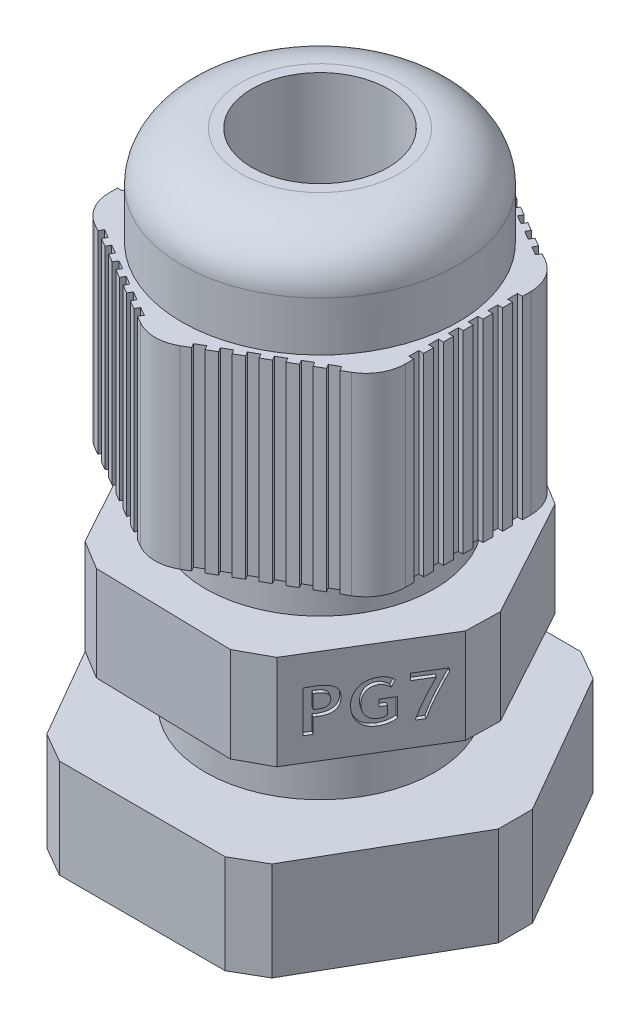
SolidWorks part; units mm, degrees
ref_plane "Front Plane" through (0, 0, 0) normal (0, 0, 1) x (1, 0, 0)
ref_plane "Top Plane" through (0, 0, 0) normal (0, 1, 0) x (1, 0, 0)
ref_plane "Right Plane" through (0, 0, 0) normal (1, 0, 0) x (0, 0, -1)
sketch "Sketch1" plane through (0, 0, 0) normal (0, 1, 0) x (1, 0, 0)
  circle A0 centre (0, 0) radius 5.8
  dimension "D1" = 11.6
extrude "Boss-Extrude1" add sketch "Sketch1" along normal blind 8.25
sketch "Sketch2" plane through (0, 8.25, 0) normal (0, 1, 0) x (1, 0, 0)
  line L1 (8.9465, -0.2087) -> (4.654, 7.6436)
  line L2 (4.654, 7.6436) -> (-4.2925, 7.8522)
  line L3 (-4.2925, 7.8522) -> (-8.9465, 0.2087)
  line L4 (-8.9465, 0.2087) -> (-4.654, -7.6436)
  line L5 (-4.654, -7.6436) -> (4.2925, -7.8522)
  line L6 (4.2925, -7.8522) -> (8.9465, -0.2087)
  circle A0 centre (0, 0) radius 7.75 construction
  dimension "D1" = 15.5
extrude "Boss-Extrude2" add sketch "Sketch2" along normal blind 4.8
sketch "Sketch3" plane through (0, 13.05, 0) normal (0, 1, 0) x (1, 0, 0)
  circle A0 centre (0, 0) radius 5.8
  dimension "D1" = 11.6
extrude "Boss-Extrude3" add sketch "Sketch3" along normal blind 2.5
sketch "Sketch4" plane through (0, 15.55, 0) normal (0, 1, 0) x (1, 0, 0)
  line L1 (7.5, 4.3301) -> (0, 8.6603)
  line L2 (0, 8.6603) -> (-7.5, 4.3301)
  line L3 (-7.5, 4.3301) -> (-7.5, -4.3301)
  line L4 (-7.5, -4.3301) -> (0, -8.6603)
  line L5 (0, -8.6603) -> (7.5, -4.3301)
  line L6 (7.5, -4.3301) -> (7.5, 4.3301)
  circle A0 centre (0, 0) radius 7.5 construction
  dimension "D1" = 15
  dimension "D2" = 0
extrude "Boss-Extrude4" add sketch "Sketch4" along normal blind 9.8
chamfer "Chamfer1" distance 1 distance2 1 6 edges at (-8.9465, 10.65, -0.2087) (-4.654, 10.65, 7.6436) (4.2925, 10.65, 7.8522) (8.9465, 10.65, 0.2087) (4.654, 10.65, -7.6436) (-4.2925, 10.65, -7.8522)
fillet "Fillet1" radius 2 6 edges at (7.5, 20.45, -4.3301) (7.5, 20.45, 4.3301) (0, 20.45, 8.6603) (-7.5, 20.45, 4.3301) (-7.5, 20.45, -4.3301) (0, 20.45, -8.6603)
sketch "Sketch5" plane through (0, 25.35, 0) normal (0, 1, 0) x (1, 0, 0)
  circle A0 centre (0, 0) radius 7
  dimension "D1" = 14
extrude "Boss-Extrude5" add sketch "Sketch5" along normal blind 5
fillet "Fillet2" radius 2.5 1 edges at (0, 30.35, 7) second distance 3 first distance on face at (0, 30.35, 7)
sketch "Sketch6" plane through (0, 30.35, 0) normal (0, 1, 0) x (1, 0, 0)
  circle A0 centre (0, 0) radius 3.45
  dimension "D1" = 6.9
extrude "Cut-Extrude1" cut sketch "Sketch6" against normal up to surface (30.35 mm away) up to face at (0, 0, 5.8)
sketch "Sketch7" plane through (-6.8002, 0, 3.7174) normal (-0.8774, 0, 0.4797) x (0.4797, 0, 0.8774)
  line L0 (-3.4745, 9.45) -> (3.4745, 9.45) construction
  line L1 (-3.4745, 13.05) -> (-3.4745, 8.25) construction
  line L2 (3.4745, 8.25) -> (3.4745, 13.05) construction
  line L3 (-3.4745, 8.25) -> (3.4745, 8.25) construction
  text T0 "<b>PG7</b>" font "Trebuchet MS" height in points 8
  dimension "D1" = 1.2
extrude "Cut-Extrude2" cut sketch "Sketch7" against normal blind 0.2
sketch "Sketch8" plane through (7.5, 0, 0) normal (1, 0, 0) x (0, 0, -1)
  line L0 (0, 25.35) -> (0, 15.55) construction
  line L1 (-3.1754, 25.35) -> (3.1754, 25.35) construction
  line L2 (-5.8, 15.55) -> (5.8, 15.55) construction
  line L3 (0.25, 25.35) -> (0.25, 15.55)
  line L4 (-0.25, 25.35) -> (-0.25, 15.55)
  line L5 (0.25, 25.35) -> (0.75, 25.35)
  line L6 (0.75, 25.35) -> (0.75, 15.55)
  line L7 (-3.1754, 15.55) -> (3.1754, 15.55) construction
  line L8 (0.75, 15.55) -> (0.25, 15.55)
  line L9 (1.75, 25.35) -> (1.75, 15.55)
  line L10 (1.25, 25.35) -> (1.25, 15.55)
  line L11 (1.25, 25.35) -> (1.75, 25.35)
  line L12 (1.75, 15.55) -> (1.25, 15.55)
  line L13 (2.75, 25.35) -> (2.75, 15.55)
  line L14 (2.25, 25.35) -> (2.25, 15.55)
  line L15 (2.25, 25.35) -> (2.75, 25.35)
  line L16 (2.75, 15.55) -> (2.25, 15.55)
  line L17 (-0.25, 25.35) -> (-0.75, 25.35)
  line L18 (-0.75, 25.35) -> (-0.75, 15.55)
  line L19 (-0.75, 15.55) -> (-0.25, 15.55)
  line L20 (-1.75, 25.35) -> (-1.75, 15.55)
  line L21 (-1.25, 25.35) -> (-1.75, 25.35)
  line L22 (-1.25, 25.35) -> (-1.25, 15.55)
  line L23 (-1.75, 15.55) -> (-1.25, 15.55)
  line L24 (-2.75, 25.35) -> (-2.75, 15.55)
  line L25 (-2.25, 25.35) -> (-2.75, 25.35)
  line L26 (-2.25, 25.35) -> (-2.25, 15.55)
  line L27 (-2.75, 15.55) -> (-2.25, 15.55)
  dimension "D1" = 2
  dimension "D3" = 0.25
  dimension "D4" = 0.25
  dimension "D5" = 0.5
  dimension "D7" = 0.5
  dimension "D8" = 0.5
  dimension "D10" = 0.5
  dimension "D2" = 2
  dimension "D6" = 3
  dimension "D9" = 3
extrude "Cut-Extrude3" cut sketch "Sketch8" against normal blind 0.25
sketch "Sketch9" plane through (0, 0, 0) normal (0, -1, 0) x (1, 0, 0)
  line L0 (-4.1962, 9) -> (-5.6962, 8.134)
  line L1 (9.8923, 0.866) -> (5.6962, 8.134)
  line L2 (4.1962, 9) -> (-4.1962, 9)
  line L3 (-5.6962, 8.134) -> (-9.8923, 0.866)
  line L4 (-9.8923, -0.866) -> (-5.6962, -8.134)
  line L5 (-4.1962, -9) -> (4.1962, -9)
  line L6 (5.6962, -8.134) -> (9.8923, -0.866)
  line L7 (-9.8923, 0.866) -> (-9.8923, -0.866)
  line L8 (5.6962, 8.134) -> (4.1962, 9)
  line L9 (9.8923, -0.866) -> (9.8923, 0.866)
  line L10 (4.1962, -9) -> (5.6962, -8.134)
  line L11 (-5.6962, -8.134) -> (-4.1962, -9)
  circle A0 centre (0, 0) radius 9 construction
  point P2 (10.3923, 0)
  point P3 (5.1962, 9)
  point P4 (-5.1962, 9)
  point P5 (-10.3923, 0)
  point P6 (-5.1962, -9)
  point P7 (5.1962, -9)
  dimension "D1" = 18
extrude "Boss-Extrude6" [suppressed] add sketch "Sketch9" against normal blind 5
sketch "Sketch10" plane through (0, 0, 0) normal (0, -1, 0) x (1, 0, 0)
  line L0 (-4.1962, 9) -> (-5.6962, 8.134)
  line L1 (9.8923, 0.866) -> (5.6962, 8.134)
  line L2 (4.1962, 9) -> (-4.1962, 9)
  line L3 (-5.6962, 8.134) -> (-9.8923, 0.866)
  line L4 (-9.8923, -0.866) -> (-5.6962, -8.134)
  line L5 (-4.1962, -9) -> (4.1962, -9)
  line L6 (5.6962, -8.134) -> (9.8923, -0.866)
  line L7 (5.6962, 8.134) -> (4.1962, 9)
  line L8 (9.8923, -0.866) -> (9.8923, 0.866)
  line L9 (-9.8923, 0.866) -> (-9.8923, -0.866)
  line L10 (-5.6962, -8.134) -> (-4.1962, -9)
  line L11 (4.1962, -9) -> (5.6962, -8.134)
  circle A0 centre (0, 0) radius 9 construction
  circle A1 centre (0, 0) radius 5.8 construction
  circle A2 centre (0, 0) radius 5.8
  point P2 (10.3923, 0)
  point P3 (5.1962, 9)
  point P4 (-5.1962, 9)
  point P5 (-10.3923, 0)
  point P6 (-5.1962, -9)
  point P7 (5.1962, -9)
  dimension "D1" = 18
extrude "Boss-Extrude7" add sketch "Sketch10" against normal blind 5
pattern_circular "CirPattern1" count 6 every 60 about axis through (0, 25.35, 0) along (0, 1, 0) of "Cut-Extrude3"
pattern_circular "CirPattern2" count 3 every 120 about axis through (0, 13.05, 0) along (0, 1, 0) of "Cut-Extrude2"
